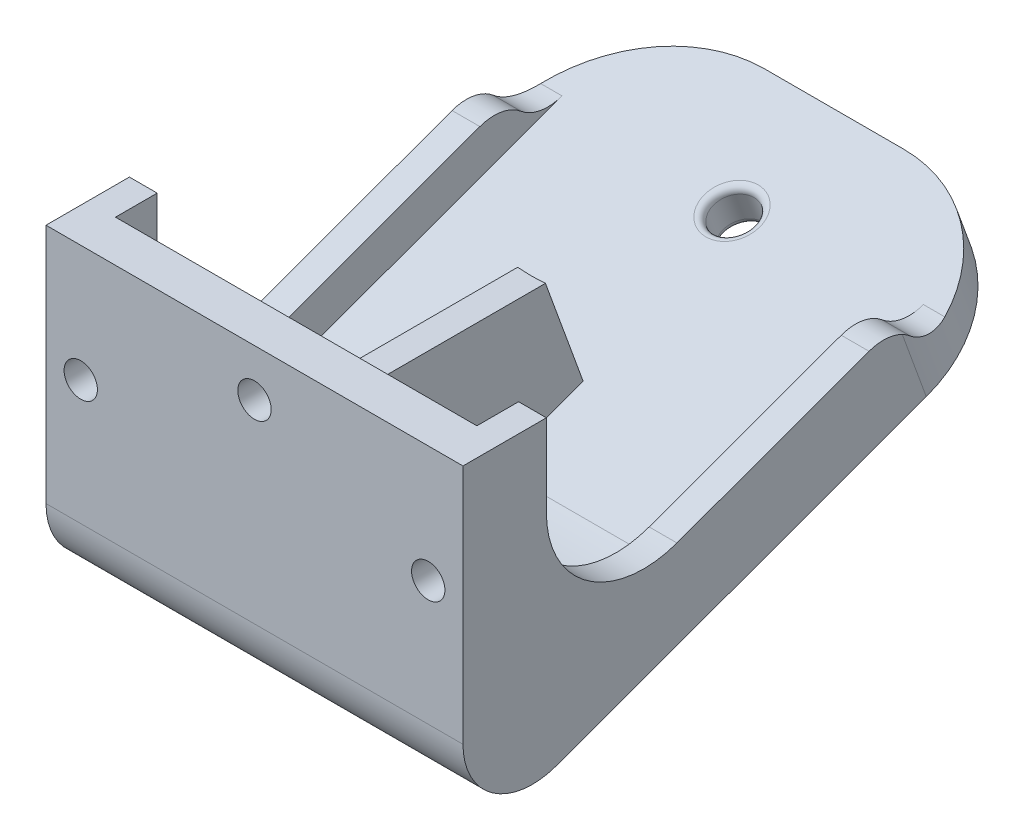
SolidWorks part; units mm, degrees
ref_plane "前视基准面" through (0, 0, 0) normal (0, 0, 1) x (1, 0, 0)
ref_plane "上视基准面" through (0, 0, 0) normal (0, 1, 0) x (1, 0, 0)
ref_plane "右视基准面" through (0, 0, 0) normal (1, 0, 0) x (0, 0, -1)
sketch "草图1" plane through (0, 0, 0) normal (0, 0, 1) x (1, 0, 0)
  line L0 (0, 20) -> (0, -20) construction
  line L1 (28.5, -20) -> (-28.5, -20) construction
  line L2 (28.5, -20) -> (28.5, 20) construction
  line L3 (28.5, 20) -> (-28.5, 20) construction
  line L4 (-28.5, -20) -> (-28.5, 20) construction
  line L5 (28.5, -20) -> (-28.5, 20) construction
  line L6 (28.5, 20) -> (-28.5, -20) construction
  line L7 (-28.5, 0) -> (28.5, 0) construction
  line L9 (32, -23.5) -> (-32, -23.5)
  line L10 (32, -23.5) -> (32, 23.5)
  line L11 (32, 23.5) -> (-32, 23.5)
  line L12 (-32, -23.5) -> (-32, 23.5)
  line L13 (32, -23.5) -> (-32, 23.5) construction
  line L14 (32, 23.5) -> (-32, -23.5) construction
  circle A0 centre (-28.5, 20) radius 1.45
  circle A1 centre (28.5, 20) radius 1.45
  circle A2 centre (28.5, -20) radius 1.45
  circle A3 centre (-28.5, -20) radius 1.45
  point P0 (0, 0)
  point P14 (0, 0)
  dimension "D3" = 3.5
  dimension "D4" = 3.5
  dimension "D5" = 2.9
  dimension "D1" = 40
  dimension "D2" = 57
extrude "凸台-拉伸1" add sketch "草图1" along normal blind 3
sketch "草图2" plane through (0, 0, 0) normal (0, 0, -1) x (-1, 0, 0)
  line L0 (32, -23.5) -> (-32, -23.5) construction
  line L1 (-22, 23.5) -> (22, 23.5)
  line L2 (-22, 23.5) -> (-22, -23.5)
  line L3 (-22, -23.5) -> (22, -23.5)
  line L4 (22, 23.5) -> (22, -23.5)
  line L5 (-22, 23.5) -> (22, -23.5) construction
  line L6 (-22, -23.5) -> (22, 23.5) construction
  line L7 (32, 23.5) -> (32, -23.5) construction
  point P0 (0, 0)
  dimension "D1" = 10
extrude "凸台-拉伸2" add sketch "草图2" along normal blind 50
sketch "草图3" plane through (-22, 0, 0) normal (-1, 0, 0) x (0, 0, 1)
  line L0 (0, -23.5) -> (-85.8433, -23.5)
  line L2 (-85.8433, -23.5) -> (-85.8433, 7.7444)
  line L3 (-85.8433, 7.7444) -> (0, -23.5)
  line L4 (0, -20.3075) -> (-50, -2.109)
  line L5 (0, -23.5) -> (0, 23.5) construction
  line L6 (0, -20.3075) -> (0, 23.5)
  line L7 (0, 23.5) -> (-50, 23.5)
  line L8 (-50, 23.5) -> (-50, -2.109)
  line L9 (-50, -23.5) -> (-50, 23.5) construction
  dimension "D1" = 20
  dimension "D2" = 3
extrude "切除-拉伸1" cut sketch "草图3" against normal blind 50
sketch "草图4" plane through (0, -20.751, -7.5528) normal (0, -0.9397, -0.342) x (1, 0, 0)
  line L1 (-32, 10.8566) -> (32, 10.8566) construction
  line L2 (22, 8.0375) -> (22, -45.1714) construction
  line L3 (-22, -46.2633) -> (22, -46.2633)
  line L4 (-22, -46.2633) -> (-22, -26.9625)
  line L5 (-22, -26.9625) -> (22, -26.9625)
  line L6 (22, -46.2633) -> (22, -26.9625)
  line L7 (22, 8.0375) -> (-22, 8.0375) construction
  circle A0 centre (0, -19.1434) radius 1.5
  dimension "D1" = 3
  dimension "D2" = 30
  dimension "D3" = 35
extrude "切除-拉伸2" cut sketch "草图4" against normal up to surface (3 mm away) up to face at (0, -11.2082, -25)
fillet "圆角2" radius 10 2 edges at (22, -10.1198, -32.3762) (-22, -10.1198, -32.3762)
sketch "草图5" plane through (0, 0, 3) normal (0, 0, 1) x (1, 0, 0)
  line L1 (-32, 23.5) -> (0, 23.5)
  line L2 (-32, 23.5) -> (-32, 0)
  line L3 (-32, 0) -> (0, 0)
  line L4 (0, 23.5) -> (0, 0)
extrude "切除-拉伸3" cut sketch "草图5" against normal blind 50
fillet "圆角3" radius 2 6 edges at (32, -23.5, 1.5) (32, 23.5, 1.5) (-32, -23.5, 1.5) (-32, 0, 1.5) (0, 23.5, 1.5) (0, 0, 1.5)
sketch "草图10" plane through (0, -20.751, -7.5528) normal (0, -0.9397, -0.342) x (1, 0, 0)
  line L2 (-22, 8.0375) -> (-22, 23.0749)
  line L3 (-22, 23.0749) -> (22, 23.0749)
  line L4 (-12, -26.9625) -> (12, -26.9625)
  line L5 (22, -16.9625) -> (22, 8.0375)
  line L6 (22, 8.0375) -> (-22, 8.0375)
  line L7 (-22, 8.0375) -> (-22, -16.9625)
  line L8 (-12, -26.9625) -> (12, -26.9625)
  line L9 (22, -16.9625) -> (22, 8.0375)
  line L11 (-22, 8.0375) -> (-22, -16.9625)
  line L12 (22, 8.0375) -> (22, 23.0749)
  circle A0 centre (0, -19.1434) radius 1.5 construction
  circle A1 centre (0, -19.1434) radius 1.5
  arc A6 (12, -26.9625) -> (22, -16.9625) centre (12, -16.9625) ccw
  arc A7 (12, -26.9625) -> (22, -16.9625) centre (12, -16.9625) ccw
  arc A8 (-22, -16.9625) -> (-12, -26.9625) centre (-12, -16.9625) ccw
  arc A9 (-22, -16.9625) -> (-12, -26.9625) centre (-12, -16.9625) ccw
  dimension "D1" = 0
extrude "凸台-拉伸6" add sketch "草图10" along normal blind 20 and the other way blind 1.7
sketch "草图11" plane through (0, 0, 3) normal (0, 0, 1) x (1, 0, 0)
  line L1 (22, -47.437) -> (-22, -47.437)
  line L2 (22, -47.437) -> (22, -23)
  line L4 (-22, -47.437) -> (-22, -23.5)
  line L6 (22, -23) -> (22, -9.6712)
  line L7 (22, -9.6712) -> (-22, -9.6712)
  line L8 (-22, -23.5) -> (-22, -9.6712)
extrude "切除-拉伸5" cut sketch "草图11" along normal blind 18
sketch "草图12" plane through (-22, 0, 0) normal (-1, 0, 0) x (0, 0, 1)
  line L0 (0, -20.3075) -> (0, -41.591)
  line L1 (0, -41.591) -> (-38.7036, -27.5041)
  line L2 (3, -45.8755) -> (-30.3327, -33.7433) construction
  line L3 (-22.4663, -12.1304) -> (0, -20.3075) construction
  line L4 (-22.4663, -12.1304) -> (-31.8632, -8.7102) construction
  line L5 (-39.7296, -30.3231) -> (-31.8632, -8.7102) construction
  line L6 (-22.4663, -12.1304) -> (0, -20.3075)
  line L7 (-22.4663, -12.1304) -> (-31.8632, -8.7102)
  line L8 (-38.7036, -27.5041) -> (-31.8632, -8.7102)
  dimension "D1" = 3
extrude "切除-拉伸6" cut sketch "草图12" against normal blind 45
fillet "圆角7" radius 10 1 edges at (0, -41.591, 0)
fillet "圆角8" radius 0.5 2 edges at (0, -32.4844, -33.7917) (0, -29.6653, -32.7656)
fillet "圆角9" radius 5 2 edges at (-22, -23.5, 1.5) (22, -23.5, 1.5)
fillet "圆角10" radius 5 1 edges at (0, -45.8755, 3)
sketch "草图13" plane through (0, 0, 0) normal (0, 0, -1) x (-1, 0, 0)
  line L0 (22.1438, -27.3095) -> (45.7453, -27.3095) construction
  line L2 (45.7453, -27.3095) -> (-48.4622, -27.3095)
  line L3 (45.7453, -27.3095) -> (45.7453, 27.256)
  line L4 (45.7453, 27.256) -> (-48.4622, 27.256)
  line L5 (-48.4622, -27.3095) -> (-48.4622, 27.256)
extrude "切除-拉伸7" cut sketch "草图13" against normal blind 10
sketch "草图14" plane through (0, -27.3095, 0) normal (0, 1, 0) x (1, 0, 0)
  line L4 (-22.1438, -3) -> (22.1438, -3)
  line L5 (22.1438, -3) -> (22.1438, 0)
  line L6 (22.1438, 0) -> (-22.1438, 0)
  line L7 (-22.1438, 0) -> (-22.1438, -3)
  line L8 (-22.1438, -3) -> (22.1438, -3)
  line L9 (22.1438, -3) -> (22.1438, 0)
  line L10 (22.1438, 0) -> (-22.1438, 0)
  line L11 (-22.1438, 0) -> (-22.1438, -3)
  dimension "D1" = 0
extrude "凸台-拉伸7" add sketch "草图14" along normal blind 55
sketch "草图15" plane through (0, 0, 3) normal (0, 0, 1) x (1, 0, 0)
  line L0 (10, 6.6905) -> (-10, 6.6905) construction
  line L1 (-22.1438, 27.6905) -> (22.1438, 27.6905) construction
  line L2 (0, 24.011) -> (10, 6.6905) construction
  circle A0 centre (0, 24.011) radius 2
  circle A1 centre (10, 6.6905) radius 2
  circle A2 centre (-10, 6.6905) radius 2
  point P0 (0, 6.6905)
  point P9 (0, 27.6905)
  dimension "D1" = 20
  dimension "D2" = 20
  dimension "D3" = 21
extrude "切除-拉伸8" cut sketch "草图15" against normal up to surface (3 mm away) up to face at (0, 0.1905, 0)
sketch "草图16" plane through (0, 0, 3) normal (0, 0, 1) x (1, 0, 0)
  line L0 (0, -43.7347) -> (0, 27.6905) construction
  line L1 (-22, -43.7347) -> (22, -43.7347) construction
  line L2 (-22.1438, 27.6905) -> (22.1438, 27.6905) construction
  line L3 (15, -43.4332) -> (15, 27.6905)
  line L4 (-15, -43.4332) -> (-15, 27.6905)
  line L5 (22, -43.7347) -> (22, -38.7347) construction
  line L6 (-22, -38.7347) -> (-22, -43.7347) construction
  line L8 (22.1438, -27.3095) -> (22.1438, 27.6905) construction
  line L9 (22.1438, 27.6905) -> (-22.1438, 27.6905) construction
  line L10 (-22.1438, 27.6905) -> (-22.1438, -27.3095) construction
  line L11 (-22, -28.5) -> (-22, -38.7347) construction
  line L12 (22, -38.7347) -> (22, -28.5) construction
  line L13 (22, -43.4332) -> (22, -38.7347)
  line L14 (-22, -38.7347) -> (-22, -43.4332)
  line L16 (22.1438, -27.3095) -> (22.1438, 27.6905)
  line L17 (22.1438, 27.6905) -> (15, 27.6905)
  line L18 (-22.1438, 27.6905) -> (-22.1438, -27.3095)
  line L19 (-22, -28.5) -> (-22, -38.7347)
  line L20 (22, -38.7347) -> (22, -28.5)
  line L22 (-15, 27.6905) -> (-22.1438, 27.6905)
  line L23 (15, -43.7347) -> (15, 27.6905) construction
  line L24 (-15, -43.7347) -> (-15, 27.6905) construction
  line L25 (22, -43.4332) -> (22, -50.9021)
  line L26 (22, -50.9021) -> (15, -50.9021)
  line L27 (15, -50.9021) -> (15, -43.4332)
  line L28 (-15, -43.4332) -> (-15, -50.9021)
  line L29 (-15, -50.9021) -> (-22, -50.9021)
  line L30 (-22, -50.9021) -> (-22, -43.4332)
  arc A0 (22.1438, -27.3095) -> (22, -28.5) centre (27, -28.5) ccw construction
  arc A1 (-22, -28.5) -> (-22.1438, -27.3095) centre (-27, -28.5) ccw construction
  arc A2 (22.1438, -27.3095) -> (22, -28.5) centre (27, -28.5) ccw
  arc A3 (-22, -28.5) -> (-22.1438, -27.3095) centre (-27, -28.5) ccw
  dimension "D1" = 15
  dimension "D2" = 15
extrude "切除-拉伸9" cut sketch "草图16" against normal blind 45
fillet "圆角11" radius 10 2 edges at (15, 27.6905, 1.5) (-15, 27.6905, 1.5)
fillet "圆角12" radius 10 2 edges at (15, -29.0711, -38.7838) (-15, -29.0711, -38.7838)
ref_plane "基准面1" through (0, 0, 0) normal (-1, 0, 0) x (0, 0, 1)
sketch "草图17" plane through (0, 0, 0) normal (-1, 0, 0) x (0, 0, 1)
  line L0 (-25.6362, -32.2602) -> (0, -12.3095)
  line L1 (0, 17.6905) -> (0, -27.3095) construction
  line L3 (0, -12.3095) -> (0, -27.3095)
  line L5 (-13.4202, -36.7065) -> (-29.3067, -30.9243) construction
  line L6 (-13.4202, -36.7065) -> (-25.6362, -32.2602)
  arc A0 (-13.4202, -36.7065) -> (0, -27.3095) centre (-10, -27.3095) ccw construction
  arc A1 (-13.4202, -36.7065) -> (0, -27.3095) centre (-10, -27.3095) ccw
  dimension "D1" = 15
  dimension "D2" = 13
extrude "凸台-拉伸8" add sketch "草图17" along normal blind 1 and the other way blind 1
sketch "草图18" plane through (15, 0, 0) normal (1, 0, 0) x (0, 0, -1)
  line L0 (0, 17.6905) -> (0, -27.3095) construction
  line L1 (13.4202, -36.7065) -> (29.3067, -30.9243) construction
  line L2 (0, 17.6905) -> (0, -27.3095)
  line L3 (13.4202, -36.7065) -> (29.3067, -30.9243)
  line L4 (3, 17.6905) -> (3, -27.3095)
  line L5 (12.3941, -33.8874) -> (28.2806, -28.1052)
  line L6 (3, 17.6905) -> (0, 17.6905)
  line L7 (28.2806, -28.1052) -> (29.3067, -30.9243)
  arc A0 (0, -27.3095) -> (13.4202, -36.7065) centre (10, -27.3095) ccw construction
  arc A1 (0, -27.3095) -> (13.4202, -36.7065) centre (10, -27.3095) ccw
  arc A2 (3, -27.3095) -> (12.3941, -33.8874) centre (10, -27.3095) ccw
  dimension "D1" = 3
extrude "凸台-拉伸9" add sketch "草图18" against normal blind 2
mirror "镜向1" about plane through (0, 0, 0) normal (-1, 0, 0) of "凸台-拉伸9"
fillet "圆角13" radius 3 4 edges at (-14, -30.9243, -29.3067) (14, -30.9243, -29.3067) (14, 17.6905, 0) (-14, 17.6905, 0)
fillet "圆角14" radius 3 4 edges at (-14, -28.1052, -28.2806) (14, -28.1052, -28.2806) (14, 17.6905, -3) (-14, 17.6905, -3)
sketch "草图19" plane through (0, -36.7258, -13.3671) normal (0, 0.9397, 0.342) x (1, 0, 0)
  circle A0 centre (0, 19.1434) radius 12.5
  dimension "D1" = 25
extrude "切除-拉伸10" cut sketch "草图19" along normal blind 19
sketch "草图20" plane through (0, 0, 3) normal (0, 0, 1) x (1, 0, 0)
  line L2 (5, -21.3919) -> (-15, -21.3919)
  line L3 (-15, -38.7347) -> (-15, 17.6905) construction
  line L4 (15, -38.7347) -> (15, 17.6905)
  line L5 (5, 27.6905) -> (-5, 27.6905)
  line L6 (-15, 17.6905) -> (-15, -38.7347)
  line L7 (-15, -38.7347) -> (15, -38.7347)
  line L8 (15, -11.3919) -> (15, 17.6905)
  line L9 (5, 27.6905) -> (-5, 27.6905)
  line L10 (-15, 17.6905) -> (-15, -10.5221)
  line L11 (-15, -38.7347) -> (15, -38.7347)
  line L12 (-15, -21.3919) -> (-15, -10.5221)
  line L13 (5, -21.3919) -> (15, -21.3919)
  line L14 (15, 17.6905) -> (15, -38.7347) construction
  line L15 (15, -21.3919) -> (15, -11.3919)
  arc A2 (15, 17.6905) -> (5, 27.6905) centre (5, 17.6905) ccw
  arc A3 (-5, 27.6905) -> (-15, 17.6905) centre (-5, 17.6905) ccw
  arc A4 (15, 17.6905) -> (5, 27.6905) centre (5, 17.6905) ccw
  arc A5 (-5, 27.6905) -> (-15, 17.6905) centre (-5, 17.6905) ccw
  dimension "D3" = 20
  dimension "D1" = 0
extrude "切除-拉伸11" cut sketch "草图20" against normal blind 20 contours L8 A4 L9 A5 L10 L12 L2 L13 L15
sketch "草图21" plane through (0, 0, 3) normal (0, 0, 1) x (1, 0, 0)
  line L0 (12.5, -29.7857) -> (-12.5, -29.7857) construction
  line L1 (0, -29.7857) -> (0, -24.7857) construction
  line L2 (0, 18.333) -> (0, -18.333) construction
  circle A0 centre (12.5, -29.7857) radius 1.2
  circle A1 centre (-12.5, -29.7857) radius 1.2
  circle A2 centre (0, -24.7857) radius 1.2
  dimension "D1" = 25
  dimension "D2" = 5
extrude "切除-拉伸13" cut sketch "草图21" against normal blind 8
sketch "草图22" plane through (0, 0, 0) normal (0, 0, -1) x (-1, 0, 0)
  line L0 (-1, -21.3919) -> (-13, -21.3919) construction
  line L1 (-7, -21.3919) -> (7.2606, -21.3919)
  line L2 (-7, -21.3919) -> (-7, -26.9796)
  line L3 (-7, -26.9796) -> (7.2606, -26.9796)
  line L4 (7.2606, -21.3919) -> (7.2606, -26.9796)
extrude "切除-拉伸14" cut sketch "草图22" along normal blind 22
ref_plane "基准面2" through (0, 0, -7) normal (0, 0, 1) x (1, 0, 0)
sketch "草图23" plane through (0, 0, -7) normal (0, 0, 1) x (1, 0, 0)
  circle A0 centre (-12.5, -29.7857) radius 1.2 construction
  circle A1 centre (12.5, -29.7857) radius 1.2 construction
  circle A2 centre (-12.5, -29.7857) radius 1.2 construction
  circle A3 centre (12.5, -29.7857) radius 1.2 construction
  circle A4 centre (12.5, -29.7857) radius 2.2
  circle A5 centre (-12.5, -29.7857) radius 2.2
extrude "切除-拉伸18" cut sketch "草图23" along normal blind 7
